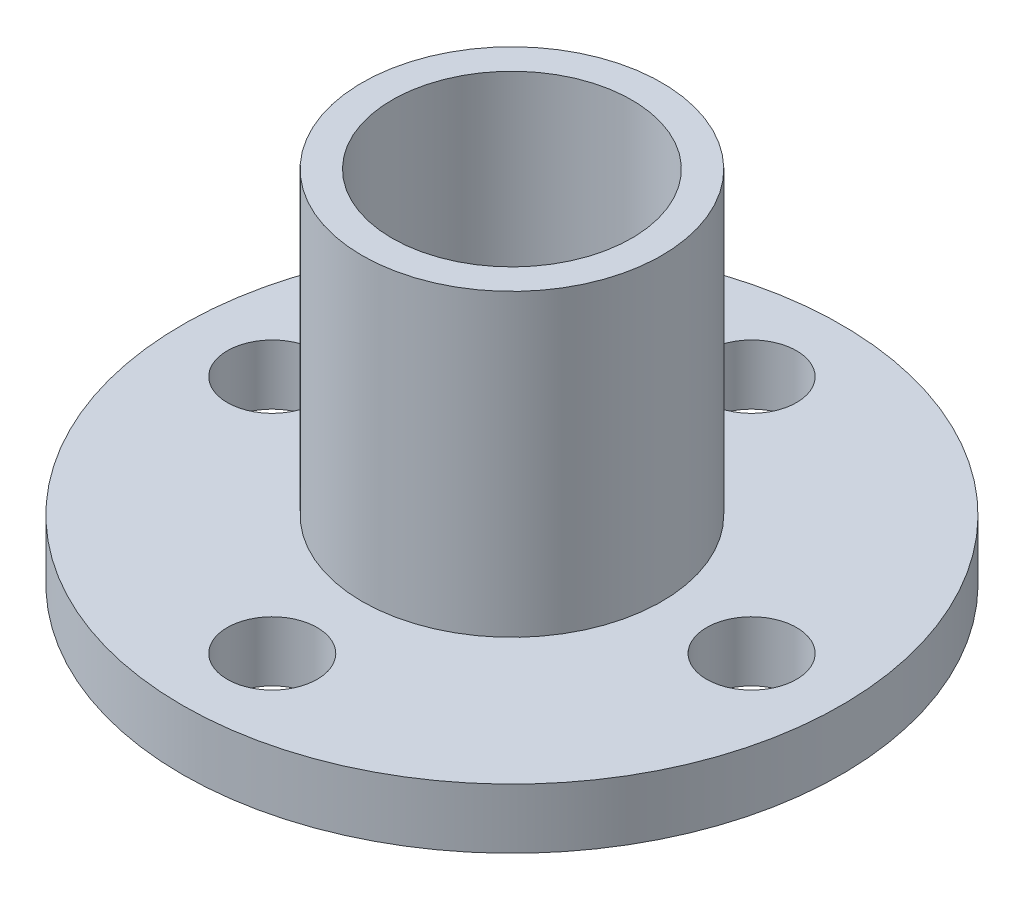
SolidWorks part; units mm, degrees
ref_plane "Front Plane" through (0, 0, 0) normal (0, 0, 1) x (1, 0, 0)
ref_plane "Top Plane" through (0, 0, 0) normal (0, 1, 0) x (1, 0, 0)
ref_plane "Right Plane" through (0, 0, 0) normal (1, 0, 0) x (0, 0, -1)
sketch "Sketch1" plane through (0, 0, 0) normal (0, 1, 0) x (1, 0, 0)
  circle A0 centre (0, 0) radius 11
  circle A1 centre (0, 0) radius 5
  circle A2 centre (0, 0) radius 4
  circle A3 centre (0, 8) radius 1.5
  circle A4 centre (8, 0) radius 1.5
  circle A5 centre (0, -8) radius 1.5
  circle A6 centre (-8, 0) radius 1.5
  point P16 (0, 0)
  dimension "D1" = 3
  dimension "D3" = 22
  dimension "D4" = 10
  dimension "D5" = 8
  dimension "D2" = 8
  dimension "D6" = 4
extrude "Boss-Extrude1" add sketch "Sketch1" along normal blind 2 contours A0 A6 A5 A4 A3 A1 region at (-10.6889, 0, 0)
extrude "Boss-Extrude2" add sketch "Sketch1<3>" along normal blind 12 contours A1 A2 region at (-4.8586, 0, 0)
sketch "Sketch1<3>" plane through (0, 0, 0) normal (0, 1, 0) x (1, 0, 0) same geometry as "Sketch1"
equation "\"screw hole\"= 3"
equation "\"outer diameter\"= 22"
equation "\"inner diameter\"= 10"
equation "\"height\"= 12"
equation "\"D1@Sketch1\"=\"screw hole\""
equation "\"D3@Sketch1\"=\"outer diameter\""
equation "\"D4@Sketch1\"=\"inner diameter\""
equation "\"D1@Boss-Extrude2\"=\"height\""
